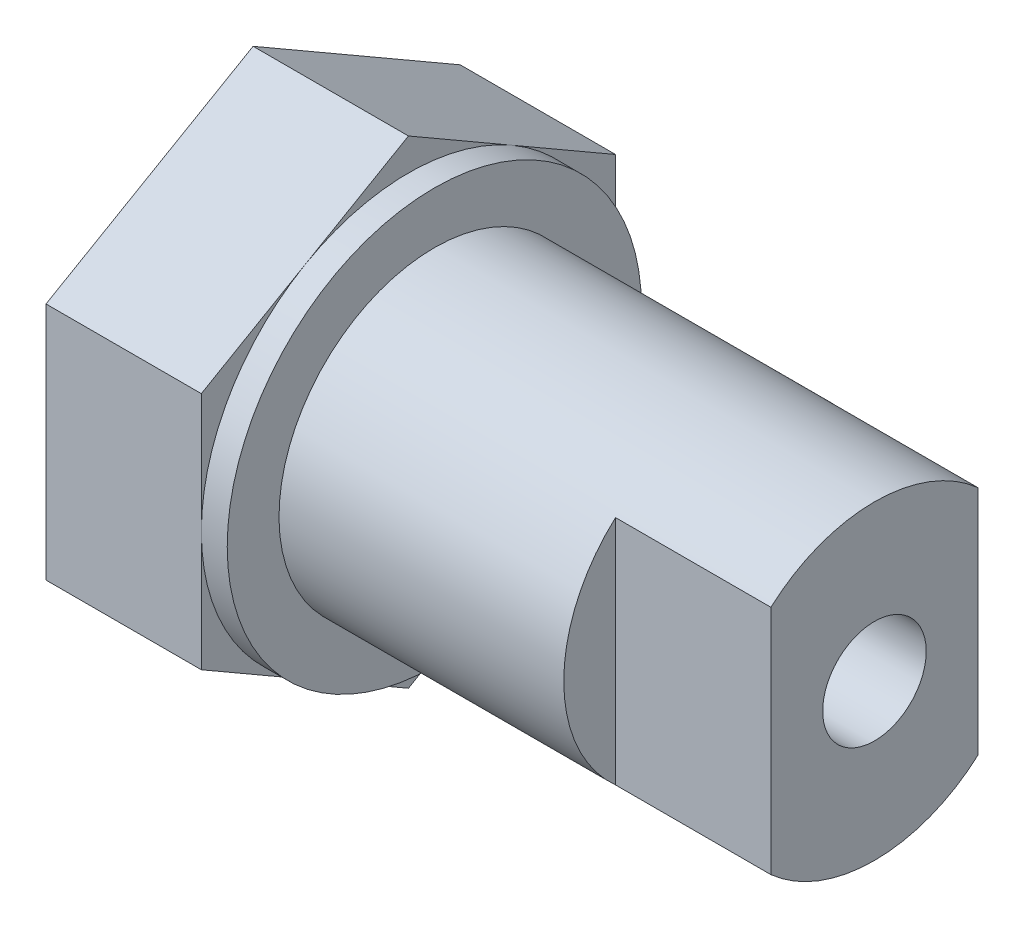
SolidWorks part; units mm, degrees
ref_plane "Front Plane" through (0, 0, 0) normal (0, 0, 1) x (1, 0, 0)
ref_plane "Top Plane" through (0, 0, 0) normal (0, 1, 0) x (1, 0, 0)
ref_plane "Right Plane" through (0, 0, 0) normal (1, 0, 0) x (0, 0, -1)
sketch "Sketch1" plane through (0, 0, 0) normal (1, 0, 0) x (0, 0, -1)
  line L1 (50.8, 29.3294) -> (0, 58.6588)
  line L2 (0, 58.6588) -> (-50.8, 29.3294)
  line L3 (-50.8, 29.3294) -> (-50.8, -29.3294)
  line L4 (-50.8, -29.3294) -> (0, -58.6588)
  line L5 (0, -58.6588) -> (50.8, -29.3294)
  line L6 (50.8, -29.3294) -> (50.8, 29.3294)
  circle A0 centre (0, 0) radius 50.8
  point P1 (0, 0)
  point P10 (0, 0)
  dimension "D1" = 50.8
extrude "Boss-Extrude1" add sketch "Sketch1" against normal blind 38.1 contours A0 L2 L3 | A0 L1 L2 | A0 | A0 L6 L1 | A0 L5 L6 | A0 L4 L5 | A0 L3 L4 region at (0, 26.2525, -45.4707) region at (0, 52.505, 0) region at (0, 0, 0) region at (0, -26.2525, -45.4707) region at (0, 26.2525, 45.4707) region at (0, -52.505, 0) region at (0, -26.2525, 45.4707)
extrude "Boss-Extrude2" add sketch "Sketch1<3>" along normal blind 6.35 contours A0 region at (0, 0, 0)
sketch "Sketch1<3>" plane through (0, 0, 0) normal (1, 0, 0) x (0, 0, -1) same geometry as "Sketch1"
sketch "Sketch2" plane through (6.35, 0, 0) normal (1, 0, 0) x (0, 0, -1)
  circle A0 centre (0, 0) radius 38.1
  dimension "D1" = 76.2
extrude "Boss-Extrude3" add sketch "Sketch2" along normal blind 107.95
sketch "Sketch3" plane through (114.3, 0, 0) normal (1, 0, 0) x (0, 0, -1)
  line L0 (0, 0) -> (0, 12.7) construction
  line L1 (-25.4, 28.3981) -> (-25.4, -28.3981)
  line L2 (25.4, 28.3981) -> (25.4, -28.3981)
  circle A0 centre (0, 0) radius 12.7
  circle A1 centre (0, 0) radius 38.1 construction
  circle M2 centre (0, 0) radius 38.1
  dimension "D1" = 25.4
  dimension "D2" = 25.4
extrude "Cut-Extrude1" cut sketch "Sketch3" against normal through all contours A0 region at (114.3, 0, 0)
extrude "Cut-Extrude2" cut sketch "Sketch3<3>" against normal blind 38.1 contours L1 M2 | L2 M2 region at (114.3, 0, 30.5604) region at (114.3, 0, -30.5604)
sketch "Sketch3<3>" plane through (114.3, 0, 0) normal (1, 0, 0) x (0, 0, -1) same geometry as "Sketch3"
